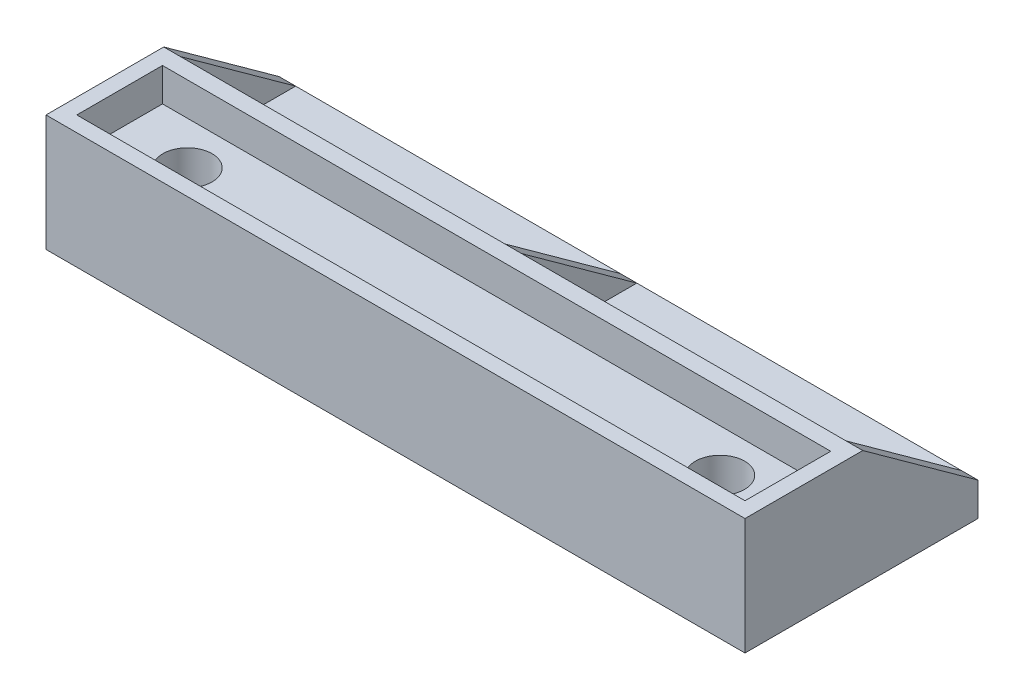
SolidWorks part; units mm, degrees
ref_plane "Front Plane" through (0, 0, 0) normal (0, 0, 1) x (1, 0, 0)
ref_plane "Top Plane" through (0, 0, 0) normal (0, 1, 0) x (1, 0, 0)
ref_plane "Right Plane" through (0, 0, 0) normal (1, 0, 0) x (0, 0, -1)
sketch "Sketch1" plane through (0, 0, 0) normal (0, 1, 0) x (1, 0, 0)
  line L1 (0, 7) -> (42, 7)
  line L2 (0, 7) -> (0, 0)
  line L3 (0, 0) -> (42, 0)
  line L4 (42, 7) -> (42, 0)
  point P0 (42, 6.7571)
  dimension "D2" = 42
  dimension "D3" = 7
extrude "Riser" add sketch "Sketch1" along normal blind 7
sketch "Sketch2" plane through (0, 0, 0) normal (0, -1, 0) x (1, 0, 0)
  line L0 (0, -7) -> (0, 0) construction
  line L1 (21, 0) -> (21, -7) construction
  line L2 (0, 0) -> (42, 0) construction
  line L4 (42, -7) -> (0, -7) construction
  circle A2 centre (5, -3.5) radius 1.475
  circle A3 centre (37, -3.5) radius 1.475
  point P2 (0, -3.5)
  dimension "D2" = 2.95
  dimension "D1" = 5
extrude "Mounting Holes" cut sketch "Sketch2" against normal through all
sketch "Sketch3" plane through (0, 7, 0) normal (0, 1, 0) x (1, 0, 0)
  line L12 (0.925, 6.075) -> (41.075, 6.075)
  line L13 (0.925, 6.075) -> (0.925, 0.925)
  line L14 (0.925, 0.925) -> (41.075, 0.925)
  line L15 (41.075, 6.075) -> (41.075, 0.925)
  line L17 (0, 7) -> (0, 0) construction
  line L18 (42, 7) -> (0, 7) construction
  dimension "D1" = 5.15
  dimension "D2" = 40.15
  dimension "D3" = 0.925
  dimension "D4" = 0.925
extrude "Recess" cut sketch "Sketch3" against normal blind 2 contours L12 L15 L14 L13
sketch "Sketch4" plane through (0, 0, 0) normal (0, 1, 0) x (1, 0, 0)
  line L1 (0, 7) -> (42, 7)
  line L2 (42, 7) -> (42, 14)
  line L3 (42, 14) -> (0, 14)
  line L4 (0, 14) -> (0, 7)
  point P0 (42, 14)
  dimension "D1" = 7
extrude "Flange" add sketch "Sketch4" along normal blind 7
sketch "Sketch5" plane through (0, 7, 0) normal (0, 1, 0) x (1, 0, 0)
  line L0 (1, 7.075) -> (1, 14)
  line L1 (42, 14) -> (0, 14) construction
  line L2 (1, 14) -> (20.5, 14)
  line L3 (20.5, 14) -> (20.5, 7.075)
  line L4 (20.5, 7.075) -> (1, 7.075)
  line L7 (42, 14) -> (0, 14) construction
  line L8 (21.5, 14) -> (41, 14)
  line L11 (0, 14) -> (0, 0) construction
  line L12 (0.925, 6.075) -> (41.075, 6.075) construction
  line L17 (21.5, 14) -> (21.5, 7.075)
  line L18 (21.5, 7.075) -> (41, 7.075)
  line L19 (41, 14) -> (41, 7.075)
  line L20 (42, 0) -> (42, 14) construction
  dimension "D1" = 1
  dimension "D2" = 1
  dimension "D3" = 1
  dimension "D4" = 1
  dimension "D5" = 19.5
extrude "Flange Cutout" cut sketch "Sketch5" against normal blind 5
sketch "Sketch7" plane through (20.5, 0, 0) normal (-1, 0, 0) x (0, 0, 1)
  line L0 (-7.075, 7) -> (-14, 2)
  line L1 (-14, 2) -> (-14, 7)
  line L2 (-14, 7) -> (-7.075, 7)
extrude "Angle Cutout" cut sketch "Sketch7" against normal through all and the other way through all
chamfer "Flange Chamfer 1" distance 1 angle 45 1 edges at (10.75, 2, -7.075)
chamfer "Flange Chamfer 2" distance 1 angle 45 1 edges at (31.25, 2, -7.075)
